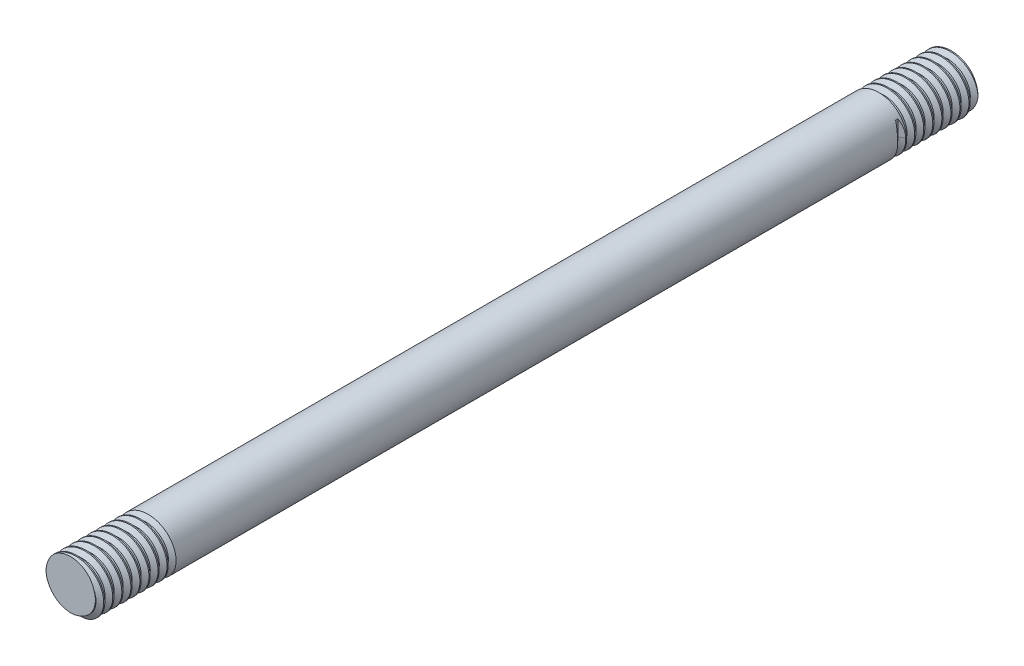
SolidWorks part; units mm, degrees
material "AISI 304"
ref_plane "Front Plane" through (0, 0, 0) normal (0, 0, 1) x (1, 0, 0)
ref_plane "Top Plane" through (0, 0, 0) normal (0, 1, 0) x (1, 0, 0)
ref_plane "Right Plane" through (0, 0, 0) normal (1, 0, 0) x (0, 0, -1)
sketch "Sketch2" plane through (0, 0, 0) normal (0, 0, 1) x (1, 0, 0)
  circle A0 centre (0, 0) radius 3
  dimension "D1" = 6
extrude "Boss-Extrude1" add sketch "Sketch2" along normal mid plane 97
thread "Thread1" pitch 1 method cut profile "Thread Profile1" start angle 0, offset 1, length 9, pitch 1, diameter 6
ref_plane "Plane1" through (-3, 0, 49.5) normal (0, -1, 0) x (-1, 0, 0)
sketch "Thread Profile1" plane through (-3, 0, 49.5) normal (0, -1, 0) x (-1, 0, 0)
  line L0 (0, 0) -> (0, 1) construction
  line L11 (0, 0) -> (0, 0.875)
  line L12 (0, 0.875) -> (-0.5413, 0.5625)
  line L13 (-0.5413, 0.5625) -> (-0.5413, 0.3125)
  line L15 (-0.5413, 0.3125) -> (0, 0)
  line L17 (-0.5413, 0.4375) -> (0, 0.4375) construction
  point P2 (0, 0)
  dimension "Pitch" = 1
  dimension "Profile_Angle" = 60
  dimension "Profile_Land" = 0.25
  dimension "Profile_Height" = 0.5413
thread "Thread2" pitch 1 method cut profile "Thread Profile2" start angle 0, offset 1, length 9, pitch 1, diameter 6
ref_plane "Plane2" through (3, 0, -49.5) normal (0, -1, 0) x (1, 0, 0)
sketch "Thread Profile2" plane through (3, 0, -49.5) normal (0, -1, 0) x (1, 0, 0)
  line L0 (0, 0) -> (0, 1) construction
  line L11 (0, 0) -> (0, 0.875)
  line L12 (0, 0.875) -> (-0.5413, 0.5625)
  line L13 (-0.5413, 0.5625) -> (-0.5413, 0.3125)
  line L15 (-0.5413, 0.3125) -> (0, 0)
  line L17 (-0.5413, 0.4375) -> (0, 0.4375) construction
  point P2 (0, 0)
  dimension "Pitch" = 1
  dimension "Profile_Angle" = 60
  dimension "Profile_Land" = 0.25
  dimension "Profile_Height" = 0.5413
sketch "Sketch11" plane through (0, 0, 0) normal (0, -1, 0) x (1, 0, 0)
  line L4 (2.4587, -40.1875) -> (3, -40.5)
  line L5 (3, -40.5) -> (3, -39.625)
  line L6 (3, -39.625) -> (2.4587, -39.9375)
  line L7 (2.4587, -39.9375) -> (2.4587, -40.1875)
  line L8 (2.4587, -40.1875) -> (3, -40.5)
  line L9 (3, -40.5) -> (3, -39.625)
  line L10 (3, -39.625) -> (2.4587, -39.9375)
  line L11 (2.4587, -39.9375) -> (2.4587, -40.1875)
  dimension "D1" = 0
extrude "Cut-Extrude1" cut sketch "Sketch11" against normal blind 97
sketch "Sketch12" plane through (0, 0, 0) normal (0, -1, 0) x (1, 0, 0)
  line L4 (-2.4587, 40.1875) -> (-3, 40.5)
  line L5 (-3, 40.5) -> (-3, 39.625)
  line L6 (-3, 39.625) -> (-2.4587, 39.9375)
  line L7 (-2.4587, 39.9375) -> (-2.4587, 40.1875)
  line L8 (-2.4587, 40.1875) -> (-3, 40.5)
  line L9 (-3, 40.5) -> (-3, 39.625)
  line L10 (-3, 39.625) -> (-2.4587, 39.9375)
  line L11 (-2.4587, 39.9375) -> (-2.4587, 40.1875)
  dimension "D1" = 0
extrude "Cut-Extrude2" cut sketch "Sketch12" against normal blind 97
